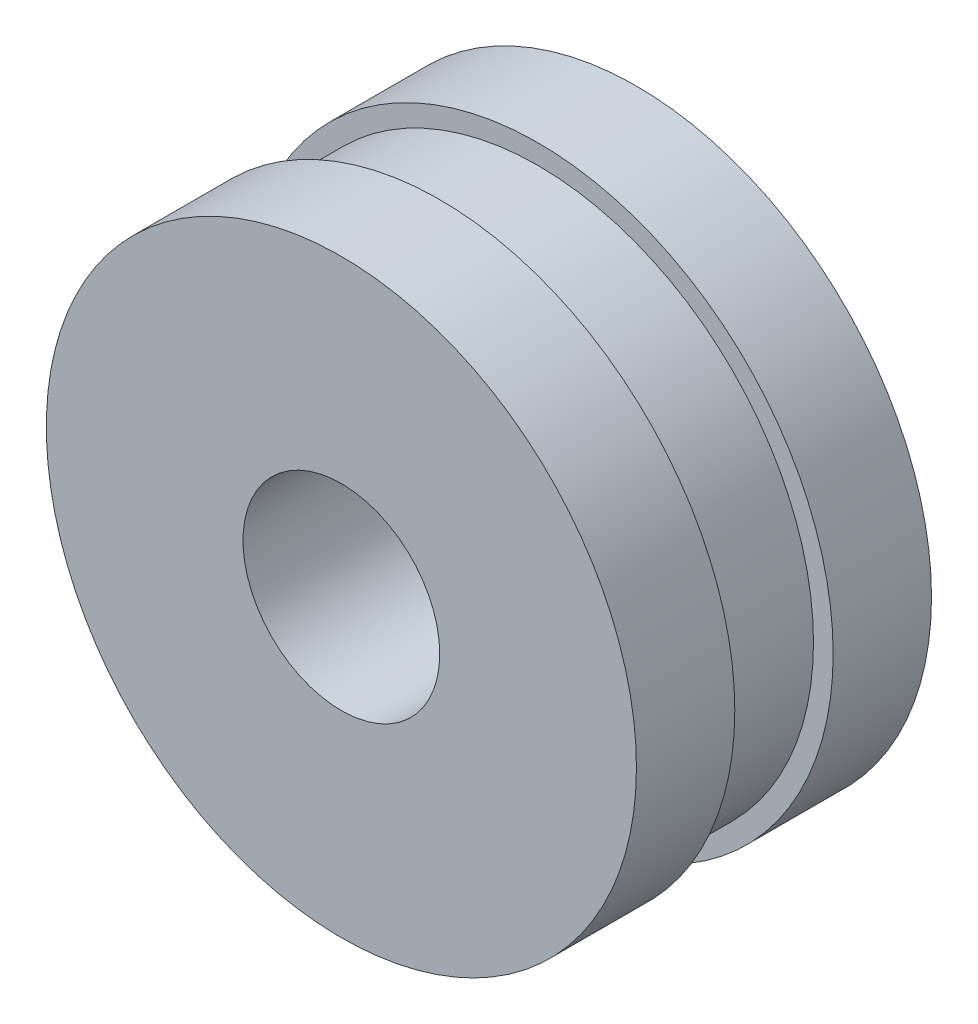
SolidWorks part; units mm, degrees
ref_plane "前视基准面" through (0, 0, 0) normal (0, 0, 1) x (1, 0, 0)
ref_plane "上视基准面" through (0, 0, 0) normal (0, 1, 0) x (1, 0, 0)
ref_plane "右视基准面" through (0, 0, 0) normal (1, 0, 0) x (0, 0, -1)
sketch "草图1" plane through (0, 0, 0) normal (0, 0, 1) x (1, 0, 0)
  circle A0 centre (0, 0) radius 3
  circle A1 centre (0, 0) radius 1
  dimension "D1" = 2
  dimension "D2" = 6
extrude "凸台-拉伸1" add sketch "草图1" along normal blind 1.5 and the other way blind 1.5
sketch "草图2" plane through (0, 0, 0) normal (0, 0, 1) x (1, 0, 0)
  circle A0 centre (0, 0) radius 3
  circle A1 centre (0, 0) radius 2.8
  circle A2 centre (0, 0) radius 3 construction
  dimension "D1" = 0.2
  dimension "D2" = 6
extrude "切除-拉伸1" cut sketch "草图2" against normal blind 0.5 and the other way blind 0.5
